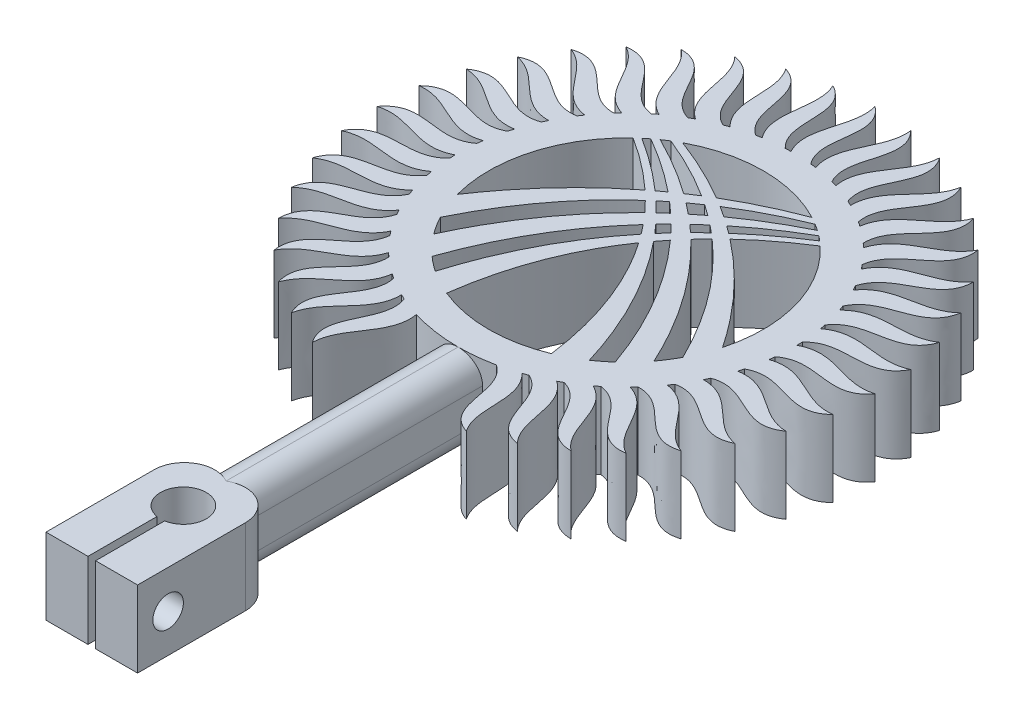
SolidWorks part; units mm, degrees
material "Plain Carbon Steel"
ref_plane "Front Plane" through (0, 0, 0) normal (0, 0, 1) x (1, 0, 0)
ref_plane "Top Plane" through (0, 0, 0) normal (0, 1, 0) x (1, 0, 0)
ref_plane "Right Plane" through (0, 0, 0) normal (1, 0, 0) x (0, 0, -1)
other "Center of Mass"
sketch "Sketch1" plane through (0, 0, 0) normal (0, 1, 0) x (1, 0, 0)
  line L1 (0, 0) -> (6, 0)
  line L2 (0, 0) -> (0, -9)
  line L3 (0, -9) -> (6, -9)
  line L4 (6, 0) -> (6, -9)
extrude "Base" add sketch "Sketch1" along normal blind 5 contours L1 L4 L3 L2
sketch "Sketch8" plane through (0, 0, 0) normal (0, 1, 0) x (1, 0, 0)
  line L0 (0, 0) -> (6, 0) construction
  line L1 (1.5, 16) -> (4.5, 16)
  line L2 (1.5, 16) -> (1.5, 0)
  line L3 (1.5, 0) -> (4.5, 0)
  line L4 (4.5, 16) -> (4.5, 0)
  line L5 (1.5, 16) -> (4.5, 0) construction
  line L6 (1.5, 0) -> (4.5, 16) construction
  point P0 (3, 8)
  dimension "D1" = 3
extrude "Handle" add sketch "Sketch8" along normal blind 5
sketch "Sketch9" plane through (0, 0, 0) normal (0, 1, 0) x (1, 0, 0)
  circle A0 centre (3, -3) radius 1.5
extrude "Motor Hole" cut sketch "Sketch9" along normal blind 5 contours A0
sketch "Sketch12" plane through (0, 0, 0) normal (1, 0, 0) x (0, 0, -1)
  circle A0 centre (-7, 2.5) radius 1
extrude "Screw Hole" cut sketch "Sketch12" along normal blind 6
sketch "Sketch13" plane through (0, 0, 0) normal (0, 1, 0) x (1, 0, 0)
  line L0 (0, -9) -> (6, -9) construction
  line L1 (2.7492, -3) -> (3.2508, -3)
  line L2 (2.7492, -3) -> (2.7492, -9)
  line L3 (2.7492, -9) -> (3.2508, -9)
  line L4 (3.2508, -3) -> (3.2508, -9)
  line L5 (2.7492, -3) -> (3.2508, -9) construction
  line L6 (2.7492, -9) -> (3.2508, -3) construction
  point P0 (3, -6)
extrude "Pinch Clamp" cut sketch "Sketch13" along normal blind 5
sketch "Sketch14" plane through (0, 0, 0) normal (0, 1, 0) x (1, 0, 0)
  circle A0 centre (3, 26) radius 11
extrude "Kyrgyz Flag" add sketch "Sketch14" along normal blind 5 separate body
sketch "Sketch17" plane through (0, 0, 0) normal (0, 1, 0) x (1, 0, 0)
  circle A0 centre (3, 26) radius 9
extrude "Inside Circle" cut sketch "Sketch17" along normal blind 5
sketch "Sketch18" plane through (0, 0, 0) normal (0, 1, 0) x (1, 0, 0)
  circle A0 centre (3, 26) radius 9 construction
  circle A1 centre (3, 26) radius 9 construction
  arc A2 (9.1272, 32.5923) -> (8.8259, 32.8599) centre (3, 26) ccw
  arc A3 (-5.6846, 23.6383) -> (-4.9469, 21.7755) centre (3, 26) ccw
  arc A4 (8.4992, 33.1245) -> (8.1465, 33.3833) centre (3, 26) ccw
  arc A5 (7.7226, 33.6614) -> (7.2328, 33.9425) centre (3, 26) ccw
  arc A6 (-4.212, 20.616) -> (-3.0007, 19.2924) centre (3, 26) ccw
  arc A7 (-2.0479, 18.5489) -> (-0.433, 17.6805) centre (3, 26) ccw
  spline S0 degree 2 poles (-5.6846, 23.6383) (-0.7963, 30.9057) (7.2328, 33.9425) knots 0 0 0 1 1 1
  spline S1 degree 2 poles (-4.9469, 21.7755) (-0.8124, 30.228) (7.7226, 33.6614) knots 0 0 0 1 1 1
  spline S2 degree 2 poles (-4.212, 20.616) (-0.2484, 29.2144) (8.1465, 33.3833) knots 0 0 0 1 1 1
  spline S3 degree 2 poles (-3.0007, 19.2924) (0.1884, 28.3324) (8.4992, 33.1245) knots 0 0 0 1 1 1
  spline S4 degree 2 poles (-2.0479, 18.5489) (0.7504, 27.7637) (8.8259, 32.8599) knots 0 0 0 1 1 1
  spline S5 degree 2 poles (-0.433, 17.6805) (0.8585, 27.3369) (9.1272, 32.5923) knots 0 0 0 1 1 1
extrude "Tunduk Left" add sketch "Sketch18" along normal blind 5
ref_plane "Mirror for Tunduk" through (3, 0, 0) normal (1, 0, 0) x (0, 0, -1)
mirror "Tunduk Right" about plane through (3, 0, 0) normal (1, 0, 0) of "Tunduk Left"
sketch "Sketch26" plane through (0, 0, 0) normal (0, 1, 0) x (1, 0, 0)
  circle A0 centre (3, 26) radius 11 construction
  circle A1 centre (3, 26) radius 11 construction
  arc A2 (4.1668, 36.9379) -> (2.8057, 36.9983) centre (3, 26) ccw
  spline S0 degree 3 poles (4.1668, 36.9379) (2.8541, 38.6346) (4.9122, 40.8915) (3, 42.3033) knots 0 0 0 0 1 1 1 1
  spline S1 degree 3 poles (3, 42.3033) (3.5366, 40.4667) (1.827, 38.8431) (2.8057, 36.9983) knots 0 0 0 0 1 1 1 1
extrude "Sunray" add sketch "Sketch26" along normal blind 5
ref_axis "Sun Axis" through (3, 27.508, -26) along (0, -1, 0)
ref_axis "Motor Axis" through (3, 15.4247, 3) along (0, -1, 0)
combine bodies "Combine2" operation type add bodies to combine 113 105
pattern_circular "CirPattern1" count 40 every 9 about axis through (3, 27.508, -26) along (0, -1, 0) skipping 19, 20, 21 of "Sunray"
fillet "Fillet1" radius 2 1 edges at (6, 2.5, 0)
fillet "Fillet2" radius 2 1 edges at (0, 2.5, 0)
fillet "Fillet4" radius 1.5 1 edges at (1.5, 5, -7.5514)
fillet "Fillet5" radius 1.5 1 edges at (4.5, 5, -7.5514)
fillet "Fillet6" radius 1.5 1 edges at (4.5, 0, -7.5514)
fillet "Fillet7" radius 1.5 1 edges at (1.5, 0, -7.5514)
other "Center of Mass Reference Point1"
ref_point "Point1"
